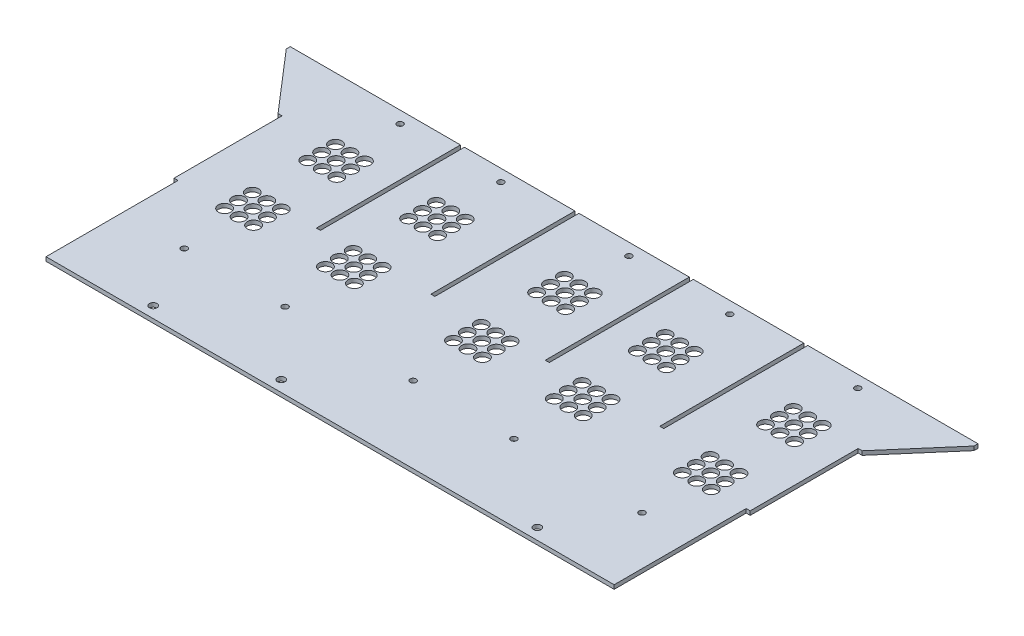
SolidWorks part; units mm, degrees
material "6061-T6 (SS)"
ref_plane "X-Y Datum" through (0, 0, 0) normal (0, 0, 1) x (1, 0, 0)
ref_plane "X-Z Datum" through (0, 0, 0) normal (0, 1, 0) x (1, 0, 0)
ref_plane "Y-Z Datum" through (0, 0, 0) normal (1, 0, 0) x (0, 0, -1)
sketch "Sketch1" plane through (0, 0, 0) normal (0, 0, 1) x (1, 0, 0)
  line L1 (-228.601, -1.5875) -> (228.601, -1.5875)
  line L2 (-228.601, -1.5875) -> (-228.601, 1.5875)
  line L3 (-228.601, 1.5875) -> (228.601, 1.5875)
  line L4 (228.601, -1.5875) -> (228.601, 1.5875)
  line L5 (-228.601, -1.5875) -> (228.601, 1.5875) construction
  line L6 (-228.601, 1.5875) -> (228.601, -1.5875) construction
  point P0 (0, 0)
  dimension "D1" = 3.175
  dimension "D2" = 457.202
extrude "Boss-Extrude1" add sketch "Sketch1" along normal blind 241.2744
sketch "Sketch2" plane through (0, 1.5875, 0) normal (0, 1, 0) x (1, 0, 0)
  line L0 (228.601, 0) -> (225.426, 0)
  line L1 (228.601, 0) -> (-228.601, 0) construction
  line L2 (225.426, 0) -> (137.796, 0)
  line L3 (137.796, 0) -> (134.621, 0)
  line L10 (134.621, 0) -> (137.796, 0)
  line L11 (134.621, 0) -> (134.621, -114.3)
  line L12 (134.621, -114.3) -> (137.796, -114.3)
  line L13 (137.796, 0) -> (137.796, -114.3)
  line M2 (228.601, 0) -> (-228.601, 0)
  dimension "D1" = 87.63
  dimension "D2" = 3.175
  dimension "D3" = 114.3
  dimension "D4" = 3.175
extrude "Cut-Extrude1" cut sketch "Sketch2" against normal through all contours L13 L11 L12 M2 region at (136.2085, 1.5875, 57.15)
pattern_linear "LPattern1" count 4 spacing 90.807 along (-1, 0, 0) of "Cut-Extrude1"
sketch "Sketch4" plane through (0, -1.5875, 0) normal (0, -1, 0) x (1, 0, 0)
  line L0 (-228.601, 0) -> (-272.876, 0)
  line L2 (-228.601, 241.2744) -> (-228.601, 0) construction
  line L3 (-228.601, 50.8) -> (-228.601, 0)
  line L4 (-272.876, 0) -> (-272.876, 3.175)
  line L6 (-228.601, 50.8) -> (-231.776, 50.8)
  line L7 (-231.776, 50.8) -> (-272.876, 3.175)
  dimension "D1" = 44.275
  dimension "D2" = 50.8
  dimension "D3" = 3.175
  dimension "D4" = 3.175
extrude "Boss-Extrude3" add sketch "Sketch4" against normal blind 3.175
mirror "Mirror1" about plane through (0, 0, 0) normal (1, 0, 0) of "Boss-Extrude3"
sketch "Sketch5" plane through (0, -1.5875, 0) normal (0, -1, 0) x (1, 0, 0)
  line L1 (-228.601, 241.2744) -> (-225.426, 241.2744)
  line L2 (-228.601, 241.2744) -> (-228.601, 136.4994)
  line L3 (-228.601, 136.4994) -> (-225.426, 136.4994)
  line L4 (-225.426, 241.2744) -> (-225.426, 136.4994)
  dimension "D1" = 3.175
  dimension "D2" = 104.775
extrude "Cut-Extrude2" cut sketch "Sketch5" against normal blind 3.175
mirror "Mirror2" about plane through (0, 0, 0) normal (1, 0, 0) of "Cut-Extrude2"
sketch "Sketch37" plane through (0, 1.5875, 0) normal (0, 1, 0) x (1, 0, 0)
  line L0 (-149.226, -241.2744) -> (-149.226, -232.3844) construction
  line L1 (225.426, -241.2744) -> (-225.426, -241.2744) construction
  line L2 (-225.426, -136.4994) -> (-225.426, -241.2744) construction
  circle A0 centre (-149.226, -232.3844) radius 3
  dimension "D1" = 8.89
  dimension "D3" = 6
  dimension "D2" = 76.2
extrude "Cut-Extrude12" cut sketch "Sketch37" against normal blind 3.175
pattern_linear "LPattern31" count 4 spacing 101.6 along (1, 0, 0) skipping (2, 0) of "Cut-Extrude12"
sketch "Sketch51" plane through (0, 1.5875, 0) normal (0, 1, 0) x (1, 0, 0)
  point P0 (-176.2216, -180.775)
  point P1 (-176.2216, -9.525)
  point P3 (-96.2064, -9.525)
  point P5 (-96.2064, -180.775)
hole_wizard "M4 Clearance Hole1" positions "Sketch55" profile "Sketch53" hole size "M4" standard "ANSI Metric" end condition up to next
sketch "Sketch55" plane through (0, 1.5875, 0) normal (0, 1, 0) x (1, 0, 0)
  point P0 (-176.2216, -180.775)
  point P3 (-176.2216, -9.525)
sketch "Sketch53" plane through (-176.2216, 1.5875, 180.775) normal (1, 0, 0) x (0, 0, 1)
  line L0 (0, 0) -> (0, 3.175)
  line L1 (0, 3.175) -> (2.4, 3.175)
  line L2 (2.4, 3.175) -> (2.4, 0)
  line L5 (2.4, 0) -> (0, 0)
  line L11 (0, -6.35) -> (0, 107.95) construction
  dimension "Thru Hole Dia." = 4.8
  dimension "Thru Hole Depth" = 3.175
hole_wizard "M4 Clearance Hole2" positions "Sketch58" profile "Sketch57" hole size "M4" standard "ANSI Metric" end condition up to next
sketch "Sketch58" plane through (0, 1.5875, 0) normal (0, 1, 0) x (1, 0, 0)
  point P0 (-96.2064, -180.775)
  point P3 (-96.2064, -9.525)
sketch "Sketch57" plane through (-96.2064, 1.5875, 180.775) normal (1, 0, 0) x (0, 0, 1)
  line L0 (0, 0) -> (0, 3.175)
  line L1 (0, 3.175) -> (2.4, 3.175)
  line L2 (2.4, 3.175) -> (2.4, 0)
  line L5 (2.4, 0) -> (0, 0)
  line L11 (0, -6.35) -> (0, 107.95) construction
  dimension "Thru Hole Dia." = 4.8
  dimension "Thru Hole Depth" = 3.175
pattern_linear "LPattern32" count 3 spacing 181.614 along (1, 0, 0) of "M4 Clearance Hole1"
pattern_linear "LPattern33" count 2 spacing 181.614 along (1, 0, 0) of "M4 Clearance Hole2"
sketch "Sketch59" plane through (0, 1.5875, 0) normal (0, 1, 0) x (1, 0, 0)
  circle A0 centre (-187.7216, -115.2567) radius 5 construction
  circle A1 centre (-176.2216, -115.2567) radius 5 construction
  circle A2 centre (-164.7216, -115.2567) radius 5 construction
  circle A3 centre (-164.7216, -126.2567) radius 5 construction
  circle A4 centre (-176.2216, -126.2567) radius 5 construction
  circle A5 centre (-187.7216, -126.2567) radius 5 construction
  circle A6 centre (-187.7216, -137.2567) radius 5 construction
  circle A7 centre (-176.2216, -137.2567) radius 5 construction
  circle A8 centre (-164.7216, -137.2567) radius 5 construction
  circle A9 centre (-187.7216, -115.2567) radius 5
  circle A10 centre (-176.2216, -115.2567) radius 5
  circle A11 centre (-164.7216, -115.2567) radius 5
  circle A12 centre (-164.7216, -126.2567) radius 5
  circle A13 centre (-176.2216, -126.2567) radius 5
  circle A14 centre (-187.7216, -126.2567) radius 5
  circle A15 centre (-187.7216, -137.2567) radius 5
  circle A16 centre (-176.2216, -137.2567) radius 5
  circle A17 centre (-164.7216, -137.2567) radius 5
  circle A18 centre (-187.7216, -71.2567) radius 5 construction
  circle A19 centre (-176.2216, -71.2567) radius 5 construction
  circle A20 centre (-164.7216, -71.2567) radius 5 construction
  circle A21 centre (-176.2216, -60.2567) radius 5 construction
  circle A22 centre (-187.7216, -60.2567) radius 5 construction
  circle A23 centre (-187.7216, -49.2567) radius 5 construction
  circle A24 centre (-176.2216, -49.2567) radius 5 construction
  circle A25 centre (-164.7216, -49.2567) radius 5 construction
  circle A26 centre (-164.7216, -60.2567) radius 5 construction
  circle A27 centre (-187.7216, -71.2567) radius 5
  circle A28 centre (-176.2216, -71.2567) radius 5
  circle A29 centre (-164.7216, -71.2567) radius 5
  circle A30 centre (-176.2216, -60.2567) radius 5
  circle A31 centre (-187.7216, -60.2567) radius 5
  circle A32 centre (-187.7216, -49.2567) radius 5
  circle A33 centre (-176.2216, -49.2567) radius 5
  circle A34 centre (-164.7216, -49.2567) radius 5
  circle A35 centre (-164.7216, -60.2567) radius 5
  circle A36 centre (-107.7064, -126.2567) radius 5 construction
  circle A37 centre (-107.7064, -115.2567) radius 5 construction
  circle A38 centre (-107.7064, -137.2567) radius 5 construction
  circle A39 centre (-96.2064, -137.2567) radius 5 construction
  circle A40 centre (-96.2064, -126.2567) radius 5 construction
  circle A41 centre (-96.2064, -115.2567) radius 5 construction
  circle A42 centre (-84.7064, -115.2567) radius 5 construction
  circle A43 centre (-84.7064, -126.2567) radius 5 construction
  circle A44 centre (-84.7064, -137.2567) radius 5 construction
  circle A45 centre (-107.7064, -126.2567) radius 5
  circle A46 centre (-107.7064, -115.2567) radius 5
  circle A47 centre (-107.7064, -137.2567) radius 5
  circle A48 centre (-96.2064, -137.2567) radius 5
  circle A49 centre (-96.2064, -126.2567) radius 5
  circle A50 centre (-96.2064, -115.2567) radius 5
  circle A51 centre (-84.7064, -115.2567) radius 5
  circle A52 centre (-84.7064, -126.2567) radius 5
  circle A53 centre (-84.7064, -137.2567) radius 5
  circle A54 centre (-84.7064, -49.2567) radius 5 construction
  circle A55 centre (-96.2064, -49.2567) radius 5 construction
  circle A56 centre (-107.7064, -49.2567) radius 5 construction
  circle A57 centre (-107.7064, -60.2567) radius 5 construction
  circle A58 centre (-107.7064, -71.2567) radius 5 construction
  circle A59 centre (-96.2064, -71.2567) radius 5 construction
  circle A60 centre (-96.2064, -60.2567) radius 5 construction
  circle A61 centre (-84.7064, -60.2567) radius 5 construction
  circle A62 centre (-84.7064, -71.2567) radius 5 construction
  circle A63 centre (-84.7064, -49.2567) radius 5
  circle A64 centre (-96.2064, -49.2567) radius 5
  circle A65 centre (-107.7064, -49.2567) radius 5
  circle A66 centre (-107.7064, -60.2567) radius 5
  circle A67 centre (-107.7064, -71.2567) radius 5
  circle A68 centre (-96.2064, -71.2567) radius 5
  circle A69 centre (-96.2064, -60.2567) radius 5
  circle A70 centre (-84.7064, -60.2567) radius 5
  circle A71 centre (-84.7064, -71.2567) radius 5
extrude "Cut-Extrude13" cut sketch "Sketch59" against normal through all contours A34 | A33 | A32 | A31 | A35 | A29 | A28 | A27 | A15 | A16 | A17 | A12 | A13 | A14 | A11 | A10 | A9 | A30 region at (-187.7216, 1.5875, 115.2567) region at (-176.2216, 1.5875, 115.2567) region at (-164.7216, 1.5875, 115.2567) region at (-164.7216, 1.5875, 126.2567) region at (-176.2216, 1.5875, 126.2567) region at (-187.7216, 1.5875, 126.2567) region at (-187.7216, 1.5875, 137.2567) region at (-176.2216, 1.5875, 137.2567) region at (-164.7216, 1.5875, 137.2567) region at (-187.7216, 1.5875, 71.2567) region at (-176.2216, 1.5875, 71.2567) region at (-164.7216, 1.5875, 71.2567) region at (-187.7216, 1.5875, 60.2567) region at (-187.7216, 1.5875, 49.2567) region at (-176.2216, 1.5875, 49.2567) region at (-164.7216, 1.5875, 49.2567) region at (-164.7216, 1.5875, 60.2567)
pattern_linear "LPattern34" count 3 spacing 181.614 along (1, 0, 0) of "Cut-Extrude13"
sketch "Sketch60" plane through (0, 1.5875, 0) normal (0, 1, 0) x (1, 0, 0)
  circle A1 centre (-164.7216, -137.2567) radius 5
  circle A2 centre (-164.7216, -137.2567) radius 5
  circle A3 centre (-176.2216, -137.2567) radius 5
  circle A4 centre (-176.2216, -137.2567) radius 5
  circle A5 centre (-187.7216, -137.2567) radius 5
  circle A6 centre (-187.7216, -137.2567) radius 5
  circle A7 centre (-187.7216, -126.2567) radius 5
  circle A8 centre (-187.7216, -126.2567) radius 5
  circle A9 centre (-176.2216, -126.2567) radius 5
  circle A10 centre (-176.2216, -126.2567) radius 5
  circle A11 centre (-164.7216, -126.2567) radius 5
  circle A12 centre (-164.7216, -126.2567) radius 5
  circle A13 centre (-164.7216, -115.2567) radius 5
  circle A14 centre (-164.7216, -115.2567) radius 5
  circle A15 centre (-176.2216, -115.2567) radius 5
  circle A16 centre (-176.2216, -115.2567) radius 5
  circle A17 centre (-187.7216, -115.2567) radius 5
  circle A18 centre (-187.7216, -115.2567) radius 5
  circle A19 centre (-164.7216, -71.2567) radius 5
  circle A20 centre (-164.7216, -71.2567) radius 5
  circle A21 centre (-176.2216, -71.2567) radius 5
  circle A22 centre (-176.2216, -71.2567) radius 5
  circle A23 centre (-187.7216, -71.2567) radius 5
  circle A24 centre (-187.7216, -71.2567) radius 5
  circle A25 centre (-164.7216, -60.2567) radius 5
  circle A26 centre (-164.7216, -60.2567) radius 5
  circle A27 centre (-164.7216, -49.2567) radius 5
  circle A28 centre (-164.7216, -49.2567) radius 5
  circle A29 centre (-176.2216, -49.2567) radius 5
  circle A30 centre (-176.2216, -49.2567) radius 5
  circle A31 centre (-187.7216, -49.2567) radius 5
  circle A32 centre (-187.7216, -49.2567) radius 5
  circle A33 centre (-187.7216, -60.2567) radius 5
  circle A34 centre (-187.7216, -60.2567) radius 5
  circle A35 centre (-176.2216, -60.2567) radius 5
  circle A36 centre (-176.2216, -60.2567) radius 5
  circle A37 centre (-84.7064, -126.2567) radius 5
  circle A38 centre (-84.7064, -126.2567) radius 5
  circle A39 centre (-84.7064, -115.2567) radius 5
  circle A40 centre (-84.7064, -115.2567) radius 5
  circle A41 centre (-96.2064, -115.2567) radius 5
  circle A42 centre (-96.2064, -115.2567) radius 5
  circle A43 centre (-96.2064, -126.2567) radius 5
  circle A44 centre (-96.2064, -126.2567) radius 5
  circle A45 centre (-96.2064, -137.2567) radius 5
  circle A46 centre (-96.2064, -137.2567) radius 5
  circle A47 centre (-107.7064, -137.2567) radius 5
  circle A48 centre (-107.7064, -137.2567) radius 5
  circle A49 centre (-107.7064, -115.2567) radius 5
  circle A50 centre (-107.7064, -115.2567) radius 5
  circle A51 centre (-107.7064, -126.2567) radius 5
  circle A52 centre (-107.7064, -126.2567) radius 5
  circle A53 centre (-84.7064, -137.2567) radius 5
  circle A54 centre (-84.7064, -137.2567) radius 5
  circle A55 centre (-84.7064, -71.2567) radius 5
  circle A56 centre (-84.7064, -71.2567) radius 5
  circle A57 centre (-84.7064, -60.2567) radius 5
  circle A58 centre (-84.7064, -60.2567) radius 5
  circle A59 centre (-96.2064, -60.2567) radius 5
  circle A60 centre (-96.2064, -60.2567) radius 5
  circle A61 centre (-96.2064, -71.2567) radius 5
  circle A62 centre (-96.2064, -71.2567) radius 5
  circle A63 centre (-107.7064, -71.2567) radius 5
  circle A64 centre (-107.7064, -71.2567) radius 5
  circle A65 centre (-107.7064, -60.2567) radius 5
  circle A66 centre (-107.7064, -60.2567) radius 5
  circle A67 centre (-107.7064, -49.2567) radius 5
  circle A68 centre (-107.7064, -49.2567) radius 5
  circle A69 centre (-96.2064, -49.2567) radius 5
  circle A70 centre (-96.2064, -49.2567) radius 5
  circle A71 centre (-84.7064, -49.2567) radius 5
  circle A72 centre (-84.7064, -49.2567) radius 5
  dimension "D1" = 0
  dimension "D2" = 0
  dimension "D3" = 0
  dimension "D4" = 0
  dimension "D5" = 0
  dimension "D6" = 0
  dimension "D7" = 0
  dimension "D8" = 0
  dimension "D9" = 0
  dimension "D10" = 0
  dimension "D11" = 0
  dimension "D12" = 0
  dimension "D13" = 0
  dimension "D14" = 0
  dimension "D15" = 0
  dimension "D16" = 0
  dimension "D17" = 0
  dimension "D18" = 0
  dimension "D19" = 0
  dimension "D20" = 0
  dimension "D21" = 0
  dimension "D22" = 0
  dimension "D23" = 0
  dimension "D24" = 0
  dimension "D25" = 0
  dimension "D26" = 0
  dimension "D27" = 0
  dimension "D28" = 0
  dimension "D29" = 0
  dimension "D30" = 0
  dimension "D31" = 0
  dimension "D32" = 0
  dimension "D33" = 0
  dimension "D34" = 0
  dimension "D35" = 0
  dimension "D36" = 0
extrude "Cut-Extrude14" cut sketch "Sketch60" against normal through all contours A48 | A46 | A54 | A38 | A52 | A44 | A40 | A42 | A50 | A72 | A58 | A60 | A70 | A68 | A64 | A66 | A62 | A56
pattern_linear "LPattern35" count 2 spacing 181.614 along (1, 0, 0) of "Cut-Extrude14"
